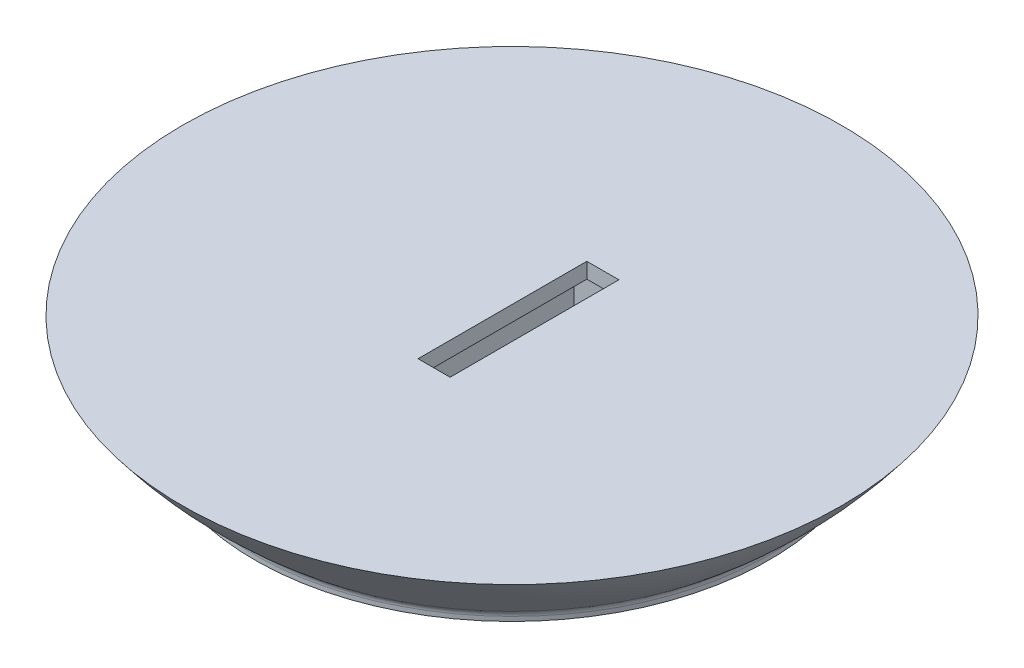
SolidWorks part; units mm, degrees
ref_plane "Front Plane" through (0, 0, 0) normal (0, 0, 1) x (1, 0, 0)
ref_plane "Top Plane" through (0, 0, 0) normal (0, 1, 0) x (1, 0, 0)
ref_plane "Right Plane" through (0, 0, 0) normal (1, 0, 0) x (0, 0, -1)
sketch "Sketch1" plane through (0, 0, 0) normal (0, 0, 1) x (1, 0, 0)
  line L0 (-45.75, -58.6097) -> (45.75, -58.6097) construction
  line L2 (-45.75, -57.8255) -> (-45.75, -58.6097) construction
  line L3 (-45.75, -58.6097) -> (0, -58.6097)
  line L5 (-45.75, -57.8255) -> (-45.75, -58.6097)
  line L6 (-58.5739, -43.8597) -> (0, -43.8597)
  line L7 (0, -43.8597) -> (0, -58.6097) construction
  line L8 (0, -43.8597) -> (0, -58.6097)
  arc A0 (46.3009, -56.664) -> (-46.3009, -56.664) centre (0, 0) ccw construction
  arc A1 (-45.75, -57.8255) -> (-46.3009, -56.664) centre (-47.25, -57.8255) ccw construction
  arc A4 (-45.75, -57.8255) -> (-46.3009, -56.664) centre (-47.25, -57.8255) ccw
  arc A6 (-58.5739, -43.8597) -> (-46.3009, -56.664) centre (0, 0) ccw
  point P3 (0, 0)
  point P13 (-4.4186, -48.6097)
  dimension "D1" = 14.75
revolve "Revolve2" add sketch "Sketch1" angle 360 about L7
sketch "Sketch2" plane through (0, -43.8597, 0) normal (0, 1, 0) x (1, 0, 0)
  line L0 (0, 0) -> (-1.7, 0) construction
  line L5 (-1.7, -15) -> (4, -15)
  line L6 (-1.7, -15) -> (-1.7, 15)
  line L7 (-1.7, 15) -> (4, 15)
  line L8 (4, -15) -> (4, 15)
  dimension "D1" = 30
  dimension "D2" = 1.7
  dimension "D3" = 4
extrude "Cut-Extrude3" cut sketch "Sketch2" against normal through all
sketch "Sketch5" plane through (0, -58.6097, 0) normal (0, -1, 0) x (1, 0, 0)
  line L0 (0, 0) -> (0, -17) construction
  line L1 (-6, -17) -> (5, -17)
  line L2 (-6, -17) -> (-6, 17)
  line L3 (-6, 17) -> (5, 17)
  line L4 (5, -17) -> (5, 17)
  line L6 (4, -15) -> (-1.7, -15) construction
  line L7 (-1.7, 15) -> (4, 15) construction
  dimension "D1" = 6
  dimension "D2" = 5
  dimension "D3" = 2
  dimension "D4" = 2
extrude "Cut-Extrude6" cut sketch "Sketch5" against normal blind 12
split "Split1" [suppressed] bodies to split 109
